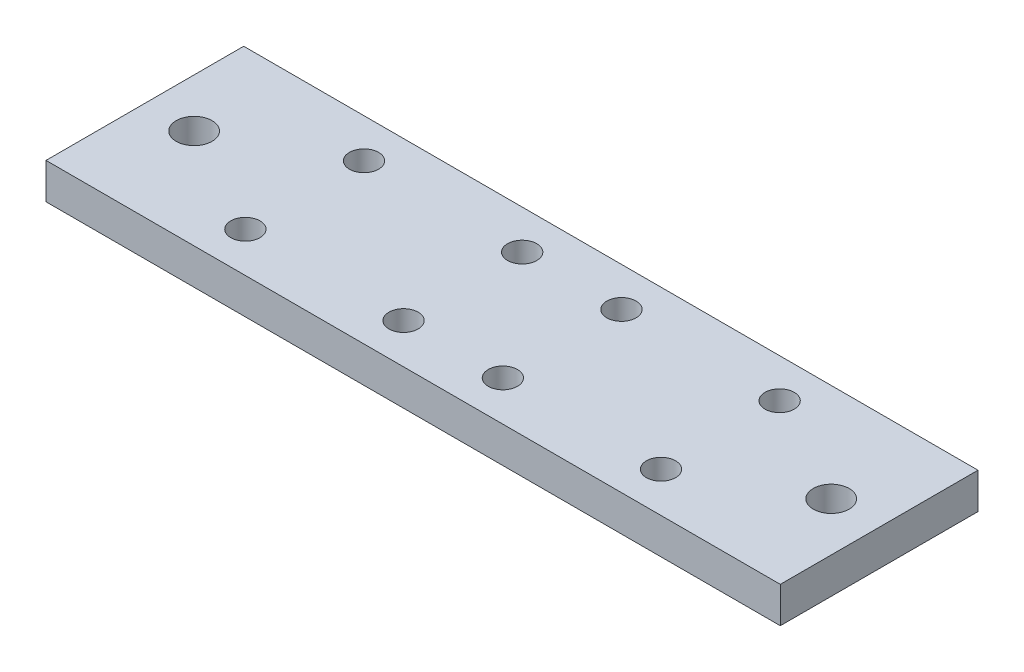
SolidWorks part; units mm, degrees
material "Alumina"
ref_plane "Front Plane" through (0, 0, 0) normal (0, 0, 1) x (1, 0, 0)
ref_plane "Top Plane" through (0, 0, 0) normal (0, 1, 0) x (1, 0, 0)
ref_plane "Right Plane" through (0, 0, 0) normal (1, 0, 0) x (0, 0, -1)
sketch "Sketch1" plane through (0, 0, 0) normal (0, 1, 0) x (1, 0, 0)
  line L1 (0, 0) -> (130, 0)
  line L2 (0, 0) -> (0, -35)
  line L3 (0, -35) -> (130, -35)
  line L4 (130, 0) -> (130, -35)
  dimension "D1" = 130
  dimension "D2" = 35
extrude "Boss-Extrude1" add sketch "Sketch1" along normal blind 6.35
sketch "Sketch5" plane through (0, 6.35, 0) normal (0, 1, 0) x (1, 0, 0)
  line L1 (0, 0) -> (0, -35) construction
  line L2 (130, -35) -> (130, 0) construction
  circle A0 centre (8.605, -17.3826) radius 3.18
  circle A2 centre (121.395, -17.3826) radius 3.18
  dimension "D1" = 8.605
  dimension "D2" = 8.605
extrude "Cut-Extrude2" cut sketch "Sketch5" against normal through all
sketch "Sketch8" plane through (0, 0, 0) normal (0, -1, 0) x (1, 0, 0)
  circle A0 centre (101.7935, 27.9113) radius 2.5866 construction
  circle A1 centre (101.7935, 6.9113) radius 2.5866 construction
  circle A2 centre (73.7935, 6.9113) radius 2.5866 construction
  circle A3 centre (73.7935, 27.9113) radius 2.5866 construction
  circle A4 centre (56.2115, 27.9113) radius 2.5866 construction
  circle A5 centre (56.2115, 6.9113) radius 2.5866 construction
  circle A6 centre (28.2115, 6.9113) radius 2.5866 construction
  circle A7 centre (28.2115, 27.9113) radius 2.5866 construction
  circle A8 centre (101.7935, 27.9113) radius 2.5866
  circle A9 centre (101.7935, 6.9113) radius 2.5866
  circle A10 centre (73.7935, 6.9113) radius 2.5866
  circle A11 centre (73.7935, 27.9113) radius 2.5866
  circle A12 centre (56.2115, 27.9113) radius 2.5866
  circle A13 centre (56.2115, 6.9113) radius 2.5866
  circle A14 centre (28.2115, 6.9113) radius 2.5866
  circle A15 centre (28.2115, 27.9113) radius 2.5866
extrude "Cut-Extrude4" cut sketch "Sketch8" against normal through all
